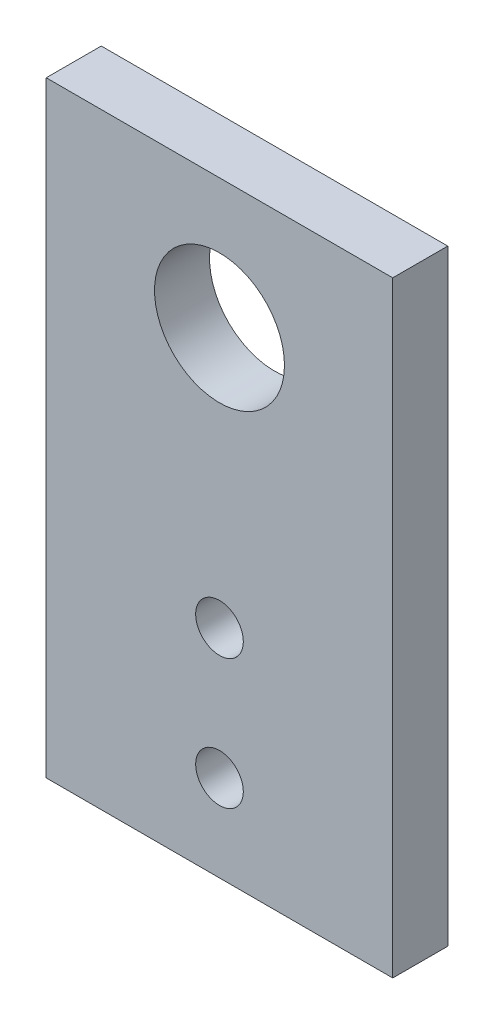
SolidWorks part; units mm, degrees
material "6061 Alloy"
ref_plane "Front Plane" through (0, 0, 0) normal (0, 0, 1) x (1, 0, 0)
ref_plane "Top Plane" through (0, 0, 0) normal (0, 1, 0) x (1, 0, 0)
ref_plane "Right Plane" through (0, 0, 0) normal (1, 0, 0) x (0, 0, -1)
sketch "Sketch1" plane through (0, 0, 0) normal (0, 0, 1) x (1, 0, 0)
  line L0 (0, 35) -> (0, -35) construction
  line L1 (-20, -35) -> (20, -35)
  line L2 (-20, -35) -> (-20, 35)
  line L3 (-20, 35) -> (20, 35)
  line L4 (20, -35) -> (20, 35)
  line L5 (-20, -35) -> (20, 35) construction
  line L6 (-20, 35) -> (20, -35) construction
  circle A0 centre (0, 20) radius 7.5
  circle A1 centre (0, -10) radius 2.5 construction
  circle A2 centre (0, -25) radius 2.5 construction
  point P4 (0, 0)
  dimension "D3" = 15
  dimension "D4" = 5
  dimension "D5" = 5
  dimension "D1" = 40
  dimension "D2" = 70
  dimension "D6" = 10
  dimension "D7" = 15
  dimension "D8" = 55
extrude "Boss-Extrude1" add sketch "Sketch1" along normal blind 6.35
hole_wizard "M5 Clearance Hole1" positions "Sketch4" profile "Sketch5" hole size "M5" standard "ISO" end condition through all
sketch "Sketch4" plane through (0, 0, 6.35) normal (0, 0, 1) x (1, 0, 0)
  point P0 (0, -10)
  point P3 (0, -25)
sketch "Sketch5" plane through (0, -10, 6.35) normal (1, 0, 0) x (0, -1, 0)
  line L0 (0, 0) -> (0, 6.35)
  line L1 (0, 6.35) -> (2.75, 6.35)
  line L2 (2.75, 6.35) -> (2.75, 0)
  line L5 (2.75, 0) -> (0, 0)
  line L11 (0, -6.35) -> (0, 107.95) construction
  dimension "Thru Hole Dia." = 5.5
  dimension "Thru Hole Depth" = 6.35
